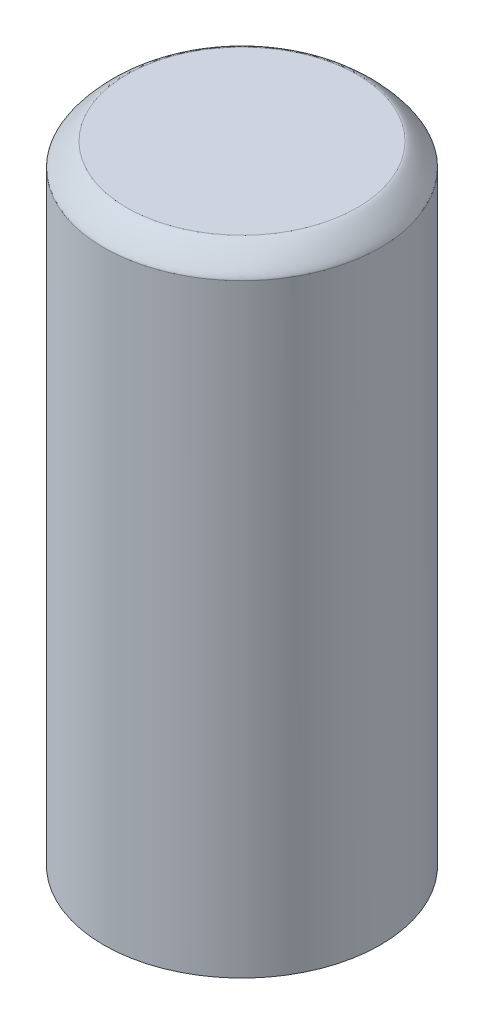
SolidWorks part; units mm, degrees
ref_plane "Front Plane" through (0, 0, 0) normal (0, 0, 1) x (1, 0, 0)
ref_plane "Top Plane" through (0, 0, 0) normal (0, 1, 0) x (1, 0, 0)
ref_plane "Right Plane" through (0, 0, 0) normal (1, 0, 0) x (0, 0, -1)
sketch "Sketch1" plane through (0, 0, 0) normal (0, 1, 0) x (1, 0, 0)
  circle A0 centre (0, 0) radius 3
  dimension "D1" = 6
extrude "Boss-Extrude1" add sketch "Sketch1" along normal blind 13.6
fillet "Fillet1" radius 0.5 1 edges at (0, 13.6, 3)
